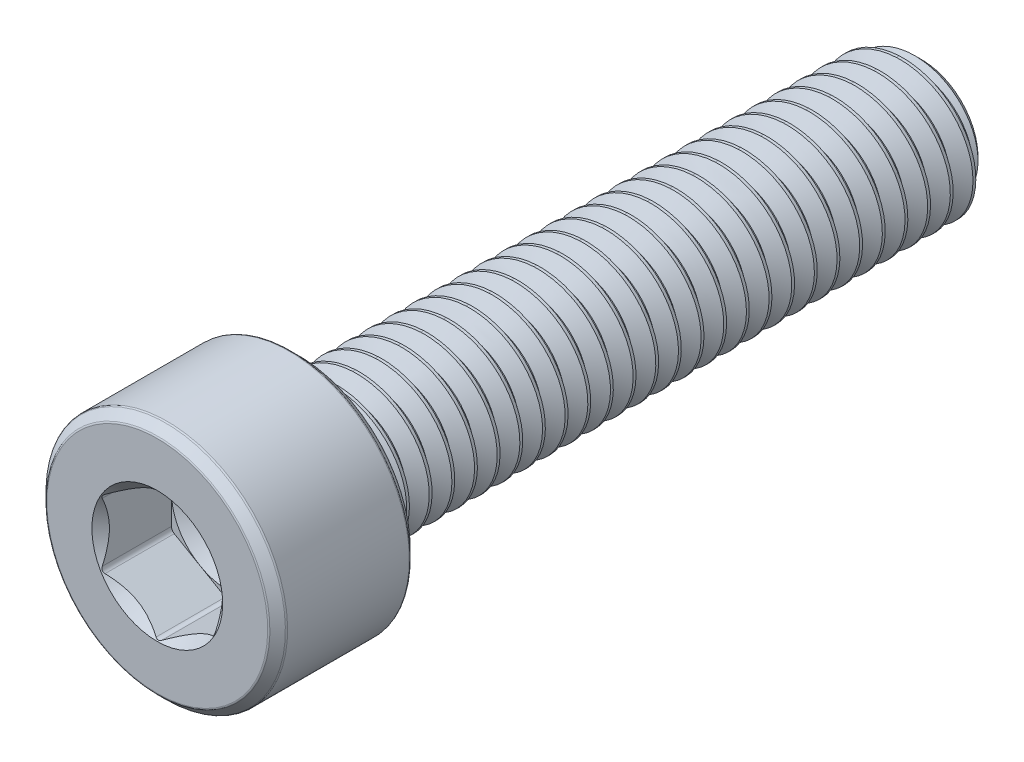
SolidWorks part; units mm, degrees
ref_plane "Front Plane" through (0, 0, 0) normal (0, 0, 1) x (1, 0, 0)
ref_plane "Top Plane" through (0, 0, 0) normal (0, 1, 0) x (1, 0, 0)
ref_plane "Right Plane" through (0, 0, 0) normal (1, 0, 0) x (0, 0, -1)
sketch "Sketch1" plane through (0, 0, 0) normal (1, 0, 0) x (0, 0, -1)
  line L0 (-13.5, 0) -> (13.5, 0) construction
  line L1 (-13.5, 0) -> (-13.5, 4.25)
  line L2 (-13.5, 4.25) -> (-8.5, 4.25)
  line L3 (-8.5, 4.25) -> (-8.5, 2.5)
  line L4 (-8.5, 2.5) -> (12.9804, 2.5)
  line L5 (13.45, 2.5866) -> (13.85, 1.8938) construction
  line L6 (13.85, 1.8938) -> (14.25, 2.5866) construction
  line L7 (14.25, 2.5866) -> (13.45, 2.5866) construction
  line L8 (12.9804, 2.5) -> (13.5, 1.9804)
  line L9 (13.5, 1.9804) -> (13.5, 0)
  line L10 (13.5, 2.5) -> (14.2, 2.5) construction
  line L11 (13.85, 2.5866) -> (13.85, 2.5) construction
  line L12 (13.85, 2.5) -> (13.85, 1.9804) construction
  line L13 (13.85, 1.9804) -> (13.85, 1.8938) construction
  line L14 (13.8, 1.9804) -> (13.9, 1.9804)
  line L15 (13.475, 2.5433) -> (14.225, 2.5433)
  line L16 (13.9, 1.9804) -> (14.225, 2.5433)
  line L17 (13.8, 1.9804) -> (13.475, 2.5433)
  line L18 (-13.5, 2) -> (-11, 2)
  line L19 (-11, 2) -> (-11, 0)
  line L20 (10.7, 2.5) -> (10.7, -2.5) construction
  point P20 (13.85, 2.5433)
  point P22 (10.7, -2.5)
  point P28 (10.7, 0)
  point P29 (12.9804, -2.5)
  dimension "Head Diameter" = 8.5
  dimension "Length" = 22
  dimension "Head Height" = 5
  dimension "Thread Size" = 5
  dimension "D1" = 45
  dimension "Thread Pitch" = 0.8
  dimension "D3" = 0.1
  dimension "Drive Size" = 4
  dimension "D4" = 2.8
  dimension "D5" = 2.5
sketch "Sketch3" plane through (0, 0, 0) normal (1, 0, 0) x (0, 0, -1)
  line L0 (-13.5, 3.8982) -> (-13.5, 2)
  line L1 (-13.5, 2) -> (-11, 2)
  line L2 (-11, 2) -> (-11, 0)
  line L3 (-11, 0) -> (13.5, 0)
  line L4 (13.5, 0) -> (13.5, 1.9804)
  line L5 (13.5, 1.9804) -> (12.9804, 2.5)
  line L6 (12.9804, 2.5) -> (-8.5, 2.5)
  line L7 (-8.5, 2.5) -> (-8.5, 3.8982)
  line L8 (-8.8518, 4.25) -> (-13.1482, 4.25)
  line L9 (-13.4767, 3.9546) -> (-13.2046, 4.2267)
  line L11 (-13.5, 4.25) -> (-8.5, 4.25) construction
  line L12 (-8.7954, 4.2267) -> (-8.5233, 3.9546)
  arc A5 (-8.5233, 3.9546) -> (-8.5, 3.8982) centre (-8.5797, 3.8982) cw
  arc A6 (-8.8518, 4.25) -> (-8.7954, 4.2267) centre (-8.8518, 4.1703) cw
  arc A7 (-13.1482, 4.25) -> (-13.2046, 4.2267) centre (-13.1482, 4.1703) ccw
  arc A8 (-13.5, 3.8982) -> (-13.4767, 3.9546) centre (-13.4203, 3.8982) cw
  point P17 (-11, 4.25)
  point P29 (-13.5, 3.9313)
  dimension "D3" = 0.0797
  dimension "D1" = 45
  dimension "D2" = 0.3187
revolve "Revolve1" add sketch "Sketch3" angle 360 about L0
sketch "Sketch4" plane through (0, 0, 13.5) normal (0, 0, 1) x (1, 0, 0)
  line L1 (0, 2.3094) -> (-2, 1.1547)
  line L2 (-2, 1.1547) -> (-2, -1.1547)
  line L3 (-2, -1.1547) -> (0, -2.3094)
  line L4 (0, -2.3094) -> (2, -1.1547)
  line L5 (2, -1.1547) -> (2, 1.1547)
  line L6 (2, 1.1547) -> (0, 2.3094)
  circle A0 centre (0, 0) radius 2 construction
extrude "Cut-Extrude1" cut sketch "Sketch4" against normal up to vertex (2.5 mm away) up to point (0, 2, 11)
sketch "Sketch5" plane through (0, 0, 13.5) normal (0, 0, 1) x (1, 0, 0)
  circle A0 centre (0, 0) radius 2.3094
extrude "Cut-Extrude2" cut sketch "Sketch5" against normal up to next (2.5 mm away) draft 45
sketch "Sketch10" plane through (0, 0, 11) normal (0, 0, 1) x (1, 0, 0)
  line L0 (2, 1.1547) -> (2, -1.1547) construction
  circle A0 centre (0, 0) radius 2
extrude "Cut-Extrude3" cut sketch "Sketch10" against normal through all draft 60
fillet "Fillet1" radius 0.2 6 edges at (-2, 1.1547, 12.25) (0, 2.3094, 12.25) (2, 1.1547, 12.25) (2, -1.1547, 12.25) (0, -2.3094, 12.25) (-2, -1.1547, 12.25)
sketch "Sketch6" plane through (0, 0, -13.5) normal (0, 0, -1) x (-1, 0, 0)
  circle A0 centre (0, 0) radius 2.5 construction
  circle A1 centre (0, 0) radius 2.5
curve "Helix/Spiral1" pitch 0.8 height 22.8 turns 28.5
sketch "Sketch7" plane through (0, 0, 0) normal (1, 0, 0) x (0, 0, -1)
  line L0 (13.8, 1.9804) -> (13.9, 1.9804) construction
  line L1 (13.8, 1.9804) -> (13.475, 2.5433) construction
  line L2 (13.475, 2.5433) -> (14.225, 2.5433) construction
  line L3 (13.9, 1.9804) -> (14.225, 2.5433) construction
  line L4 (13.8, 1.9804) -> (13.9, 1.9804)
  line L5 (13.8, 1.9804) -> (13.475, 2.5433)
  line L6 (13.475, 2.5433) -> (14.225, 2.5433)
  line L7 (13.9, 1.9804) -> (14.225, 2.5433)
sweep "Cut-Sweep1" cut profiles "Sketch7" path "Helix/Spiral1"
sketch "Sketch11" plane through (0, 0, 0) normal (1, 0, 0) x (0, 0, -1)
  line L0 (-8.5, 2.7) -> (-8.3, 2.5) construction
  line L1 (-8.5, 4.25) -> (-8.5, 2.5) construction
  line L2 (-8.5, 2.5) -> (12.9804, 2.5) construction
  line L3 (-8.3, 2.5) -> (-8.1, 2.5)
  line L4 (-8.1, 2.5) -> (-5.6, 0)
  line L5 (-13.5, 0) -> (13.5, 0) construction
  line L6 (-5.6, 0) -> (-8.5, 0)
  line L7 (-8.5, 0) -> (-8.5, 2.7) construction
  line L8 (-8.5, 2.7) -> (-9.8453, 2.7)
  line L9 (-9.8453, 2.7) -> (-9.8453, 0)
  line L10 (-9.8453, 0) -> (-8.5, 0)
  arc A0 (-8.3, 2.5) -> (-8.5, 2.7) centre (-8.3, 2.7) cw
  dimension "D1" = 45
  dimension "D2" = 0.2
  dimension "D3" = 45
  dimension "D4" = 0.4
revolve "Revolve2" add sketch "Sketch11" angle 360 about L6
equation "\"D3@Sketch1\" = \"Thread Pitch@Sketch1\" / 8"
equation "\"D4@Sketch1\" = \"Thread Pitch@Sketch1\" * 3.5"
equation "\"D3@Helix/Spiral1\" = \"Length@Sketch1\" + \"Thread Pitch@Sketch1\""
equation "\"D4@Helix/Spiral1\" = \"Thread Pitch@Sketch1\""
equation "\"D5@Sketch1\"=\"Head Height@Sketch1\"*0.5"
equation "\"D2@Sketch3\"=\"Head Diameter@Sketch1\" *0.0375"
equation "\"D2@Sketch11\"=\"Thread Pitch@Sketch1\" / 4"
equation "\"D4@Sketch11\"=\"Thread Pitch@Sketch1\"/2"
equation "\"D1@Fillet1\"=\"Drive Size@Sketch1\"*0.05"
equation "\"D1@Fillet1\" = \"Drive Size@Sketch1\" * 0.05"
equation "\"D3@Sketch3\"=\"D2@Sketch3\"*0.25"
